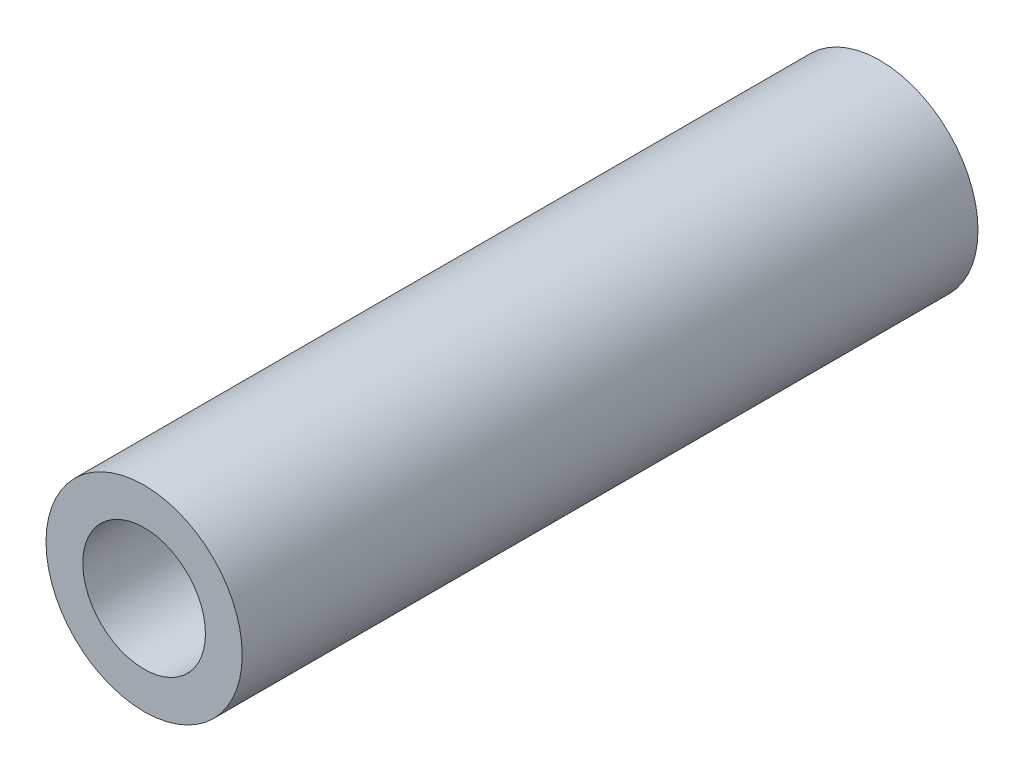
SolidWorks part; units mm, degrees
material "Brass"
ref_plane "Front Plane" through (0, 0, 0) normal (0, 0, 1) x (1, 0, 0)
ref_plane "Top Plane" through (0, 0, 0) normal (0, 1, 0) x (1, 0, 0)
ref_plane "Right Plane" through (0, 0, 0) normal (1, 0, 0) x (0, 0, -1)
sketch "Sketch1" plane through (0, 0, 0) normal (0, 0, 1) x (1, 0, 0)
  circle A0 centre (0, 0) radius 1.6
  circle A1 centre (0, 0) radius 1
  dimension "D1" = 3.2
  dimension "D2" = 2
extrude "Boss-Extrude1" add sketch "Sketch1" along normal blind 12
